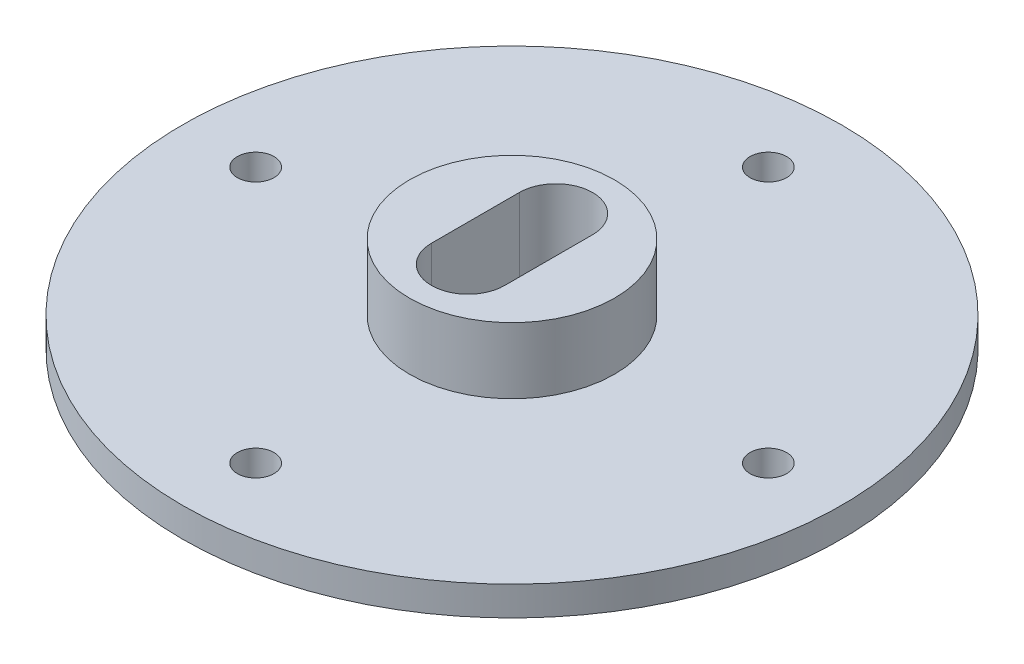
SolidWorks part; units mm, degrees
ref_plane "Front Plane" through (0, 0, 0) normal (0, 0, 1) x (1, 0, 0)
ref_plane "Top Plane" through (0, 0, 0) normal (0, 1, 0) x (1, 0, 0)
ref_plane "Right Plane" through (0, 0, 0) normal (1, 0, 0) x (0, 0, -1)
sketch "Sketch1" plane through (0, 0, 0) normal (0, 1, 0) x (1, 0, 0)
  circle A0 centre (0, 0) radius 35 construction
  circle A1 centre (0, 0) radius 45
  circle A2 centre (0, 35) radius 2.5
  circle A3 centre (35, 0) radius 2.5
  circle A4 centre (0, -35) radius 2.5
  circle A5 centre (-35, 0) radius 2.5
  circle A6 centre (0, 0) radius 14
  point P15 (0, 0)
  dimension "D1" = 70
  dimension "D2" = 90
  dimension "D3" = 5
  dimension "D5" = 28
  dimension "D4" = 4
extrude "Boss-Extrude1" add sketch "Sketch1" along normal blind 4 contours A1 A6 A5 A4 A3 A2 | A6 region at (-43.7272, 0, 0) region at (0, 0, 0)
extrude "Boss-Extrude2" add sketch "Sketch1<3>" along normal blind 13 contours A6
sketch "Sketch1<3>" plane through (0, 0, 0) normal (0, 1, 0) x (1, 0, 0) same geometry as "Sketch1"
sketch "Sketch3" plane through (0, 13, 0) normal (0, 1, 0) x (1, 0, 0)
  line L0 (0, -6) -> (0, 6) construction
  line L1 (-5, -6) -> (-5, 6)
  line L2 (5, -6) -> (5, 6)
  line L3 (-5, 0) -> (5, 0) construction
  arc A0 (-5, -6) -> (5, -6) centre (0, -6) ccw
  arc A1 (5, 6) -> (-5, 6) centre (0, 6) ccw
  point P2 (0, 0)
  dimension "D1" = 12
  dimension "D2" = 10
extrude "Cut-Extrude1" cut sketch "Sketch3" against normal through all
